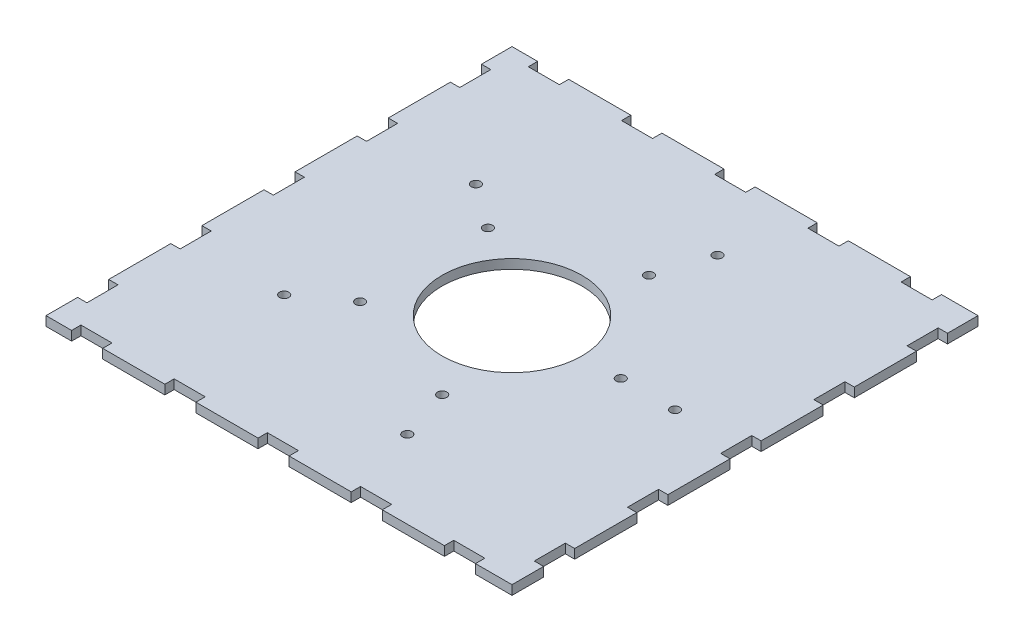
SolidWorks part; units mm, degrees
ref_plane "Front Plane" through (0, 0, 0) normal (0, 0, 1) x (1, 0, 0)
ref_plane "Top Plane" through (0, 0, 0) normal (0, 1, 0) x (1, 0, 0)
ref_plane "Right Plane" through (0, 0, 0) normal (1, 0, 0) x (0, 0, -1)
sketch "Sketch1" plane through (0, 0, 0) normal (0, 1, 0) x (-1, 0, 0)
  line L0 (75, -75) -> (-75, -75)
  line L1 (-75, -75) -> (-75, 75)
  line L2 (-75, 75) -> (75, 75)
  line L3 (75, 75) -> (75, -75)
  dimension "D1" = 150
  dimension "D2" = 150
extrude "Boss-Extrude1" add sketch "Sketch1" along normal blind 3 contours L0 L1 L2 L3
sketch "Sketch2" plane through (0, 3, 0) normal (0, 1, 0) x (1, 0, 0)
  circle A0 centre (0, 0) radius 22.5
  dimension "D1" = 45
extrude "Cut-Extrude1" cut sketch "Sketch2" against normal blind 3
sketch "Sketch3" plane through (0, 3, 0) normal (0, 1, 0) x (1, 0, 0)
  line L0 (-66.75, 75) -> (-66.75, 72)
  line L1 (-75, 75) -> (75, 75) construction
  line L2 (-66.75, 72) -> (-56.75, 72)
  line L3 (-56.75, 72) -> (-56.75, 75)
  line L4 (-56.75, 75) -> (-66.75, 75)
  line L5 (-75, 0) -> (75, 0) construction
  line L6 (-75, -75) -> (-75, 75) construction
  line L7 (75, 75) -> (75, -75) construction
  line L8 (-56.75, -75) -> (-66.75, -75)
  line L9 (-56.75, -72) -> (-56.75, -75)
  line L10 (-66.75, -72) -> (-56.75, -72)
  line L11 (-66.75, -75) -> (-66.75, -72)
  dimension "D1" = 10
  dimension "D2" = 3
extrude "Cut-Extrude2" cut sketch "Sketch3" against normal blind 3
pattern_linear "LPattern1" count 5 spacing 30 along (1, 0, 0) of "Cut-Extrude2"
sketch "Sketch4" plane through (0, 3, 0) normal (0, 1, 0) x (1, 0, 0)
  line L0 (-75, -64.8253) -> (-72, -64.8253)
  line L1 (-75, -75) -> (-75, 75) construction
  line L2 (-72, -64.8253) -> (-72, -54.8253)
  line L3 (-72, -54.8253) -> (-75, -54.8253)
  line L4 (-75, -54.8253) -> (-75, -64.8253)
  line L5 (0, 72) -> (0, -72) construction
  line L6 (-6.75, 72) -> (3.25, 72) construction
  line L7 (3.25, -72) -> (-6.75, -72) construction
  line L8 (75, -54.8253) -> (75, -64.8253)
  line L9 (72, -54.8253) -> (75, -54.8253)
  line L10 (72, -64.8253) -> (72, -54.8253)
  line L11 (75, -64.8253) -> (72, -64.8253)
  dimension "D1" = 10
  dimension "D2" = 3
extrude "Cut-Extrude3" cut sketch "Sketch4" against normal blind 3
pattern_linear "LPattern2" count 5 spacing 30 along (0, 0, -1) of "Cut-Extrude3"
sketch "Sketch5" plane through (0, 0, 0) normal (0, -1, 0) x (-1, 0, 0)
  circle A2 centre (-35, 0) radius 1.5
  circle A3 centre (-52.5, 0) radius 1.5
  circle A4 centre (-10.8156, 33.287) radius 1.5
  circle A5 centre (28.3156, 20.5725) radius 1.5
  circle A6 centre (28.3156, -20.5725) radius 1.5
  circle A7 centre (-10.8156, -33.287) radius 1.5
  circle A8 centre (-16.2234, 49.9305) radius 1.5
  circle A9 centre (42.4734, 30.8587) radius 1.5
  circle A10 centre (42.4734, -30.8587) radius 1.5
  circle A11 centre (-16.2234, -49.9305) radius 1.5
  point P18 (0, 0)
  point P27 (0, 0)
  dimension "D3" = 3
  dimension "D4" = 2
  dimension "D5" = 5
  dimension "D6" = 5
extrude "Cut-Extrude5" cut sketch "Sketch5" against normal blind 3 contours A2
extrude "Cut-Extrude6" cut sketch "Sketch5<3>" against normal blind 3
sketch "Sketch5<3>" plane through (0, 0, 0) normal (0, -1, 0) x (-1, 0, 0) same geometry as "Sketch5"
